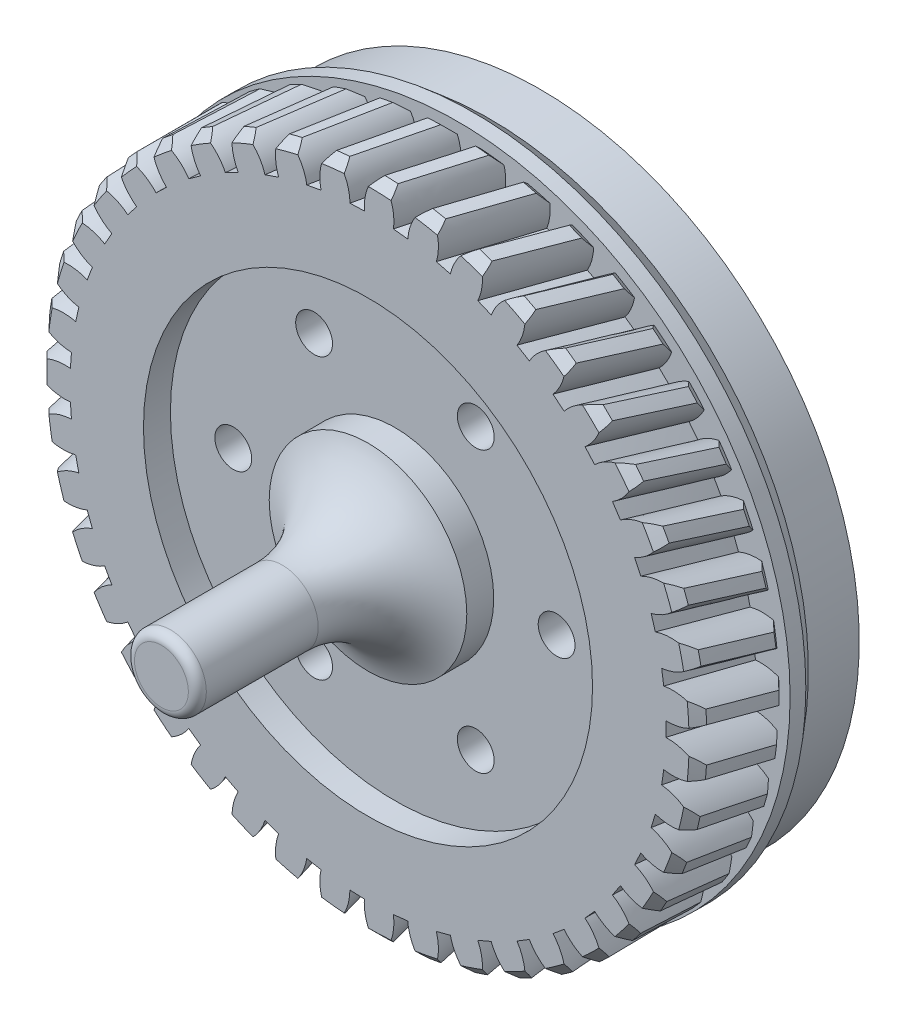
SolidWorks part; units mm, degrees
ref_plane "Front Plane" through (0, 0, 0) normal (1, 0, 0) x (0, 1, 0)
ref_plane "Top Plane" through (0, 0, 0) normal (0, 0, 1) x (0, 1, 0)
ref_plane "Right Plane" through (0, 0, 0) normal (0, 1, 0) x (-1, 0, 0)
sketch "Sketch5" plane through (0, 0, 0) normal (0, 0, 1) x (0, 1, 0)
  circle A0 centre (0, 0) radius 36.75
  dimension "D1" = 73.5
extrude "Boss-Extrude1" add sketch "Sketch5" along normal blind 10
chamfer "Chamfer1" distance 1 angle 45 2 edges at (36.75, 0, 10) (36.75, 0, 0)
sketch "Sketch9" plane through (0, 0, 10) normal (0, 0, 1) x (1, 0, 0)
  circle A0 centre (0, 0) radius 36.75 construction
  circle A1 centre (0, 0) radius 36.75
curve "Helix/Spiral1" pitch 869.5652 height 20 radius 36.75 centre (0, 0, 10) axis (0, 0, -1) start towards (1, 0, 0)
sketch "Sketch10" plane through (0, 0, 10) normal (0, 0, 1) x (1, 0, 0)
  line L0 (0, 0) -> (33.1645, 0) construction
  line L1 (33.1645, 0.8085) -> (33.1645, -0.8085)
  arc A2 (33.1645, 0.8085) -> (36.9375, 2.15) centre (33.3745, 6.1944) ccw
  arc A3 (33.1645, -0.8085) -> (36.9375, -2.15) centre (33.3745, -6.1944) cw
  arc A5 (36.9375, -2.15) -> (36.9375, 2.15) centre (0, 0) ccw
  point P9 (33.1645, 0)
  dimension "D2" = 4.3
  dimension "D4" = 5.39
  dimension "D5" = 74
  dimension "D1" = 1.617
  dimension "D3" = 3.773
sweep "Cut-Sweep1" cut profiles "Sketch10" path "Helix/Spiral1" align with end faces yes
pattern_circular "CirPattern1" count 43 over 360 about axis through (0, 0, 10) along (0, 0, -1) of "Cut-Sweep1" reverse direction yes
sketch "Sketch12" plane through (0, 0, 0) normal (0, 0, 1) x (0, 1, 0)
  circle A0 centre (0, 0) radius 4
  dimension "D1" = 8
extrude "Boss-Extrude2" add sketch "Sketch12" along normal blind 23 from surface starting at face at (0, 0, 10)
sketch "Sketch13" plane through (0, 0, 0) normal (0, 0, 1) x (0, 1, 0)
  circle A0 centre (0, 0) radius 11
  circle A1 centre (0, 0) radius 25
  dimension "D1" = 50
  dimension "D2" = 22
extrude "Cut-Extrude2" cut sketch "Sketch13" against normal blind 3 from surface starting at face at (4, 0, 10)
sketch "Sketch14" plane through (0, 0, 0) normal (0, 0, 1) x (0, 1, 0)
  circle A6 centre (15.5885, 9) radius 2.05
  circle A7 centre (15.5885, -9) radius 2.05
  circle A8 centre (0, -18) radius 2.05
  circle A9 centre (-15.5885, -9) radius 2.05
  circle A10 centre (-15.5885, 9) radius 2.05
  circle A11 centre (0, 0) radius 18 construction
  circle A12 centre (0, 18) radius 2.05
  point P24 (0, 0)
  dimension "D1" = 4.1
  dimension "D3" = 4.1
  dimension "D4" = 4.1
  dimension "D5" = 4.1
  dimension "D6" = 4.1
  dimension "D7" = 4.1
  dimension "D2" = 18
fillet "Fillet1" radius 1 1 edges at (4, 0, 33)
fillet "Fillet2" radius 10 1 edges at (4, 0, 10)
sketch "Sketch17" plane through (0, 0, 0) normal (0, 1, 0) x (-1, 0, 0)
  line L3 (-35.5, -9.2) -> (0, -9.2)
  line L4 (0, -9.2) -> (0, 0)
  line L5 (0, 0) -> (-37, 0)
  line L10 (-37, 0) -> (-37, -1.75)
  line L13 (-37, -1.75) -> (-35.5, -3.5376)
  line L14 (-35.5, -3.5376) -> (-35.5, -9.2)
  line L15 (-37, -1.75) -> (0, -1.75) construction
  dimension "D1" = 35.5
  dimension "D2" = 9.2
  dimension "D3" = 37
  dimension "D4" = 1.75
  dimension "D5" = 50
revolve "Revolve1" add sketch "Sketch17" angle 360 about L4
extrude "Cut-Extrude3" cut sketch "Sketch14" against normal blind 20 from surface starting at face at (11, 0, 7)
